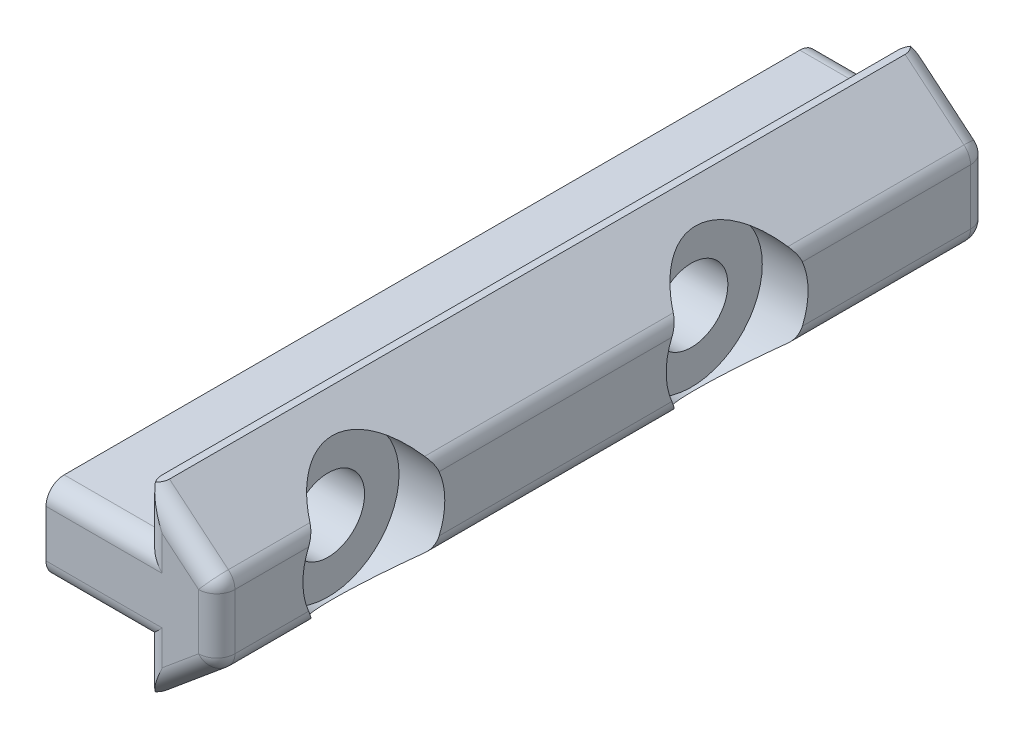
SolidWorks part; units mm, degrees
ref_plane "Front Plane" through (0, 0, 0) normal (0, 0, 1) x (1, 0, 0)
ref_plane "Top Plane" through (0, 0, 0) normal (0, 1, 0) x (1, 0, 0)
ref_plane "Right Plane" through (0, 0, 0) normal (1, 0, 0) x (0, 0, -1)
ref_plane "Plane1" through (0, 0, 23.6855) normal (0, 0, 1) x (1, 0, 0)
sketch "Sketch1" plane through (0, 0, 23.6855) normal (0, 0, 1) x (1, 0, 0)
  line L0 (3.302, 6.35) -> (-4.064, 6.35)
  line L1 (-4.064, 6.35) -> (-4.064, -6.35)
  line L2 (-4.064, -6.35) -> (3.302, -6.35)
  line L3 (3.302, -6.35) -> (7.874, -2.54)
  line L4 (7.874, -2.54) -> (7.874, 2.54)
  line L5 (7.874, 2.54) -> (3.302, 6.35)
extrude "Boss-Extrude1" add sketch "Sketch1" against normal blind 53.975
sketch "Sketch2" plane through (0, 0, 23.6855) normal (0, 0, 1) x (1, 0, 0)
  line L0 (-4.064, 6.35) -> (-4.064, 2.921)
  line L1 (-4.064, 2.921) -> (2.794, 2.921)
  line L2 (2.794, 2.921) -> (2.794, 6.35)
  line L3 (2.794, 6.35) -> (-4.064, 6.35)
extrude "Cut-Extrude1" cut sketch "Sketch2" against normal through all
sketch "Sketch3" plane through (0, 2.921, 0) normal (0, 1, 0) x (-1, 0, 0)
  line L0 (4.064, -30.1669) -> (0, -30.1669)
  line L1 (0, -30.1669) -> (0, 23.8081)
  line L2 (0, 23.8081) -> (4.064, 23.8081)
  line L3 (4.064, 23.8081) -> (4.064, -30.1669)
  dimension "D1" = 53.975
extrude "Boss-Extrude2" [suppressed] add sketch "Sketch3" along normal blind 7.366
sketch "Sketch4" plane through (0, 0, 23.6855) normal (0, 0, 1) x (1, 0, 0)
  line L0 (-4.064, -6.35) -> (2.794, -6.35)
  line L1 (2.794, -6.35) -> (2.794, -2.921)
  line L2 (2.794, -2.921) -> (-4.064, -2.921)
  line L3 (-4.064, -2.921) -> (-4.064, -6.35)
extrude "Cut-Extrude2" cut sketch "Sketch4" against normal through all
sketch "Sketch5" plane through (0, -2.921, 0) normal (0, -1, 0) x (1, 0, 0)
  line L0 (0, -33.4644) -> (-4.064, -33.4644)
  line L1 (-4.064, -33.4644) -> (-4.064, 20.5106)
  line L2 (-4.064, 20.5106) -> (0, 20.5106)
  line L3 (0, 20.5106) -> (0, -33.4644)
  dimension "D1" = 53.975
extrude "Boss-Extrude3" [suppressed] add sketch "Sketch5" along normal blind 7.366
hole_wizard "#3 Clearance Hole1" positions "Sketch7" profile "Sketch6" hole size "#3" standard "ANSI Inch"
sketch "Sketch7" plane through (-4.064, 0, 0) normal (-1, 0, 0) x (0, 0, 1)
  point P0 (12.7, 0)
  point P1 (-12.7, 0)
sketch "Sketch6" plane through (-4.064, 0, 12.7) normal (0, 1, 0) x (0, 0, 1)
  line L0 (0, 0) -> (0, 11.938)
  line L1 (0, 11.938) -> (1.3843, 11.938)
  line L2 (1.3843, 11.938) -> (1.3843, 0)
  line L5 (1.3843, 0) -> (0, 0)
  line L11 (0, -6.35) -> (0, 107.95) construction
  dimension "Thru Hole Dia." = 2.7686
  dimension "Thru Hole Depth" = 11.938
sketch "Sketch12" plane through (7.874, 0, 0) normal (1, 0, 0) x (0, 0, -1)
  line L0 (-12.7, 1.3843) -> (-12.7, -1.3843) construction
  line L1 (12.7, 1.3843) -> (12.7, -1.3843) construction
  circle A0 centre (-12.7, 0) radius 1.3843 construction
  circle A1 centre (12.7, 0) radius 1.3843 construction
  point P5 (-12.7, 0)
  point P11 (12.7, 0)
hole_wizard "CBORE for #10 Button Head Cap Screw1" positions "Sketch13" profile "Sketch14" counterbore size "#10" standard "ANSI Inch" end condition through all
sketch "Sketch13" plane through (7.874, 0, 0) normal (1, 0, 0) x (0, 0, -1)
  point P0 (-12.7, 0)
  point P3 (12.7, 0)
sketch "Sketch14" plane through (7.874, 0, 12.7) normal (0, 1, 0) x (0, 0, -1)
  line L0 (0, 0) -> (0, 11.938)
  line L1 (0, 11.938) -> (2.5527, 11.938)
  line L3 (2.5527, 11.938) -> (2.5527, 3.2004)
  line L4 (2.5527, 3.2004) -> (4.9606, 3.2004)
  line L5 (4.9606, 3.2004) -> (4.9606, 0)
  line L7 (4.9606, 0) -> (0, 0)
  line L11 (0, -6.35) -> (0, 107.95) construction
  dimension "Thru Hole Dia." = 5.1054
  dimension "Thru Hole Depth" = 11.938
  dimension "C'Bore Dia." = 9.9212
  dimension "C'Bore Depth" = 3.2004
fillet "Fillet1" radius 1.27 6 edges at (7.874, -2.54, 20.3233) (7.874, -2.54, -23.6253) (7.874, -2.54, 0) (7.874, 2.54, 20.3233) (7.874, 2.54, 0) (7.874, 2.54, -23.6253)
fillet "Fillet3" radius 1.27 9 edges at (5.3595, -4.6354, -30.2895) (7.7541, -2.4838, -30.2895) (5.3595, 4.6354, -30.2895) (7.7541, 2.4838, -30.2895) (-0.635, -2.921, -30.2895) (-0.635, 2.921, -30.2895) (2.794, 4.6355, -30.2895) (2.794, -4.6355, -30.2895) (7.874, 0, -30.2895)
fillet "Fillet5" radius 1.27 9 edges at (5.3595, -4.6354, 23.6855) (7.7541, -2.4838, 23.6855) (5.3595, 4.6354, 23.6855) (7.7541, 2.4838, 23.6855) (2.794, 4.6355, 23.6855) (-0.635, 2.921, 23.6855) (-0.635, -2.921, 23.6855) (2.794, -4.6355, 23.6855) (7.874, 0, 23.6855)
sketch "Sketch15" plane through (-4.064, 0, 0) normal (-1, 0, 0) x (0, 0, 1)
  line L1 (23.6855, 10.3219) -> (-30.2895, 10.3219)
  line L2 (23.6855, 10.3219) -> (23.6855, -9.9981)
  line L3 (23.6855, -9.9981) -> (-30.2895, -9.9981)
  line L4 (-30.2895, 10.3219) -> (-30.2895, -9.9981)
  line L5 (23.6855, 10.3219) -> (-30.2895, -9.9981) construction
  line L6 (23.6855, -9.9981) -> (-30.2895, 10.3219) construction
  point P0 (-3.302, 0.1619)
  dimension "D1" = 20.32
